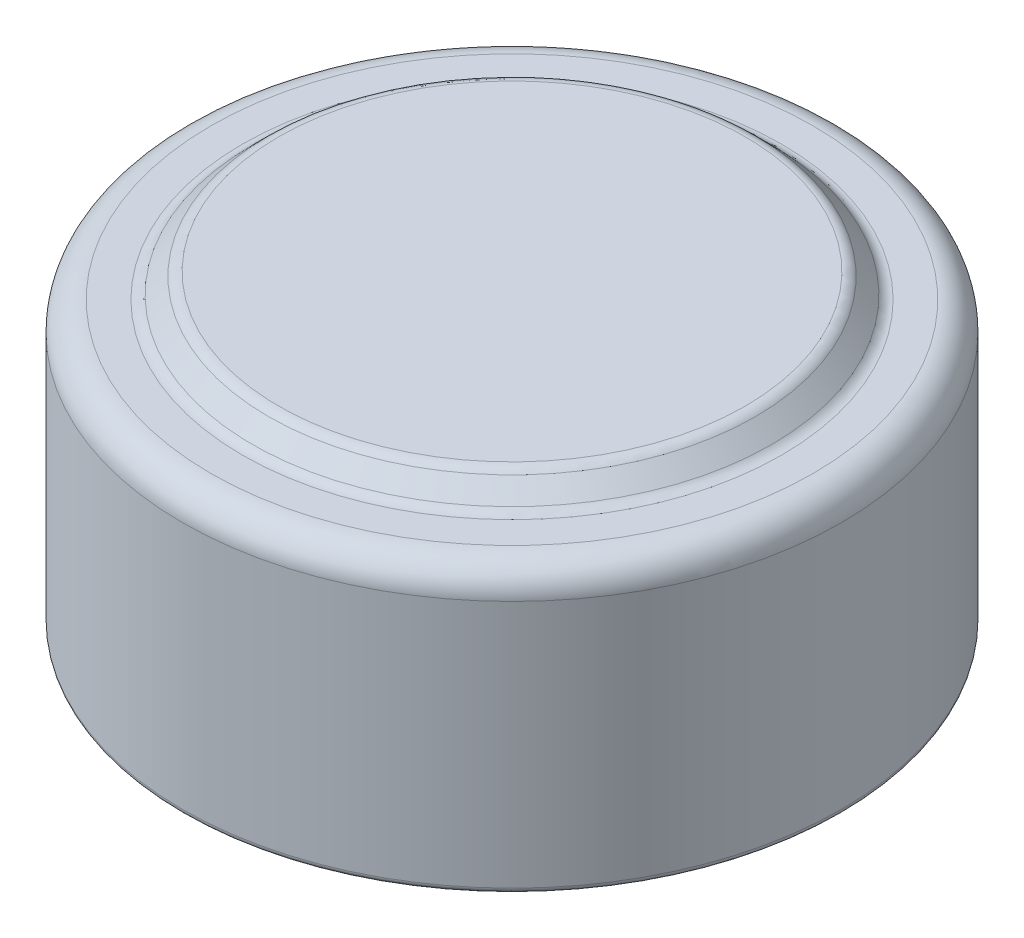
SolidWorks part; units mm, degrees
ref_plane "Front Plane" through (0, 0, 0) normal (0, 0, 1) x (1, 0, 0)
ref_plane "Top Plane" through (0, 0, 0) normal (0, 1, 0) x (1, 0, 0)
ref_plane "Right Plane" through (0, 0, 0) normal (1, 0, 0) x (0, 0, -1)
sketch "Sketch1" plane through (0, 0, 0) normal (0, 0, 1) x (1, 0, 0)
  line L0 (0, 0) -> (-5.7, 0)
  line L1 (-5.8, 0.1) -> (-5.8, 4.47)
  line L2 (-4.1064, 5.4) -> (0, 5.4)
  line L3 (0, 5.4) -> (0, 0)
  line L4 (-4.2832, 5.3268) -> (-4.5668, 5.0432)
  line L7 (-5.3, 4.97) -> (-4.7436, 4.97)
  arc A0 (-5.8, 4.47) -> (-5.3, 4.97) centre (-5.3, 4.47) cw
  arc A1 (-4.2832, 5.3268) -> (-4.1064, 5.4) centre (-4.1064, 5.15) cw
  arc A2 (-4.7436, 4.97) -> (-4.5668, 5.0432) centre (-4.7436, 5.22) ccw
  arc A3 (-5.7, 0) -> (-5.8, 0.1) centre (-5.7, 0.1) cw
  point P9 (-5.8, 4.97)
  point P14 (-4.21, 5.4)
  point P17 (-5.8, 0)
  point P18 (-4.64, 4.97)
  dimension "D6" = 0.5
  dimension "D7" = 0.25
  dimension "D8" = 0.1
  dimension "D1" = 5.8
  dimension "D2" = 5.4
  dimension "D3" = 4.64
  dimension "D4" = 4.97
  dimension "D5" = 45
revolve "Revolve1" add sketch "Sketch1" angle 360 about L3
sketch "Sketch2" plane through (0, 0, 0) normal (0, -1, 0) x (1, 0, 0)
  line L0 (0.25, 0.25) -> (2, 0.25)
  line L1 (-0.25, 2) -> (0.25, 2)
  line L2 (-0.25, 2) -> (-0.25, 0.25)
  line L3 (-0.25, -2) -> (0.25, -2)
  line L4 (0.25, 2) -> (0.25, 0.25)
  line L5 (-2, 0.25) -> (-0.25, 0.25)
  line L6 (-2, 0.25) -> (-2, -0.25)
  line L7 (-2, -0.25) -> (-0.25, -0.25)
  line L8 (2, 0.25) -> (2, -0.25)
  line L9 (0.25, -0.25) -> (2, -0.25)
  line L10 (0.25, -0.25) -> (0.25, -2)
  line L11 (-0.25, -0.25) -> (-0.25, -2)
  circle A0 centre (0, 0) radius 4 construction
  text T0 "                                 LR44" font "Century Gothic" height 1
  dimension "D1" = 8
  dimension "D2" = 2
  dimension "D3" = 0.5
  dimension "D4" = 0.25
  dimension "D5" = 4
  dimension "D6" = 0.5
  dimension "D7" = 0.25
  dimension "D8" = 4
  dimension "D9" = 2
wrap "Wrap1" sketch "Sketch2" wrap type scribe source sketch "Sketch2" face at (-5.7, 0, 0)
